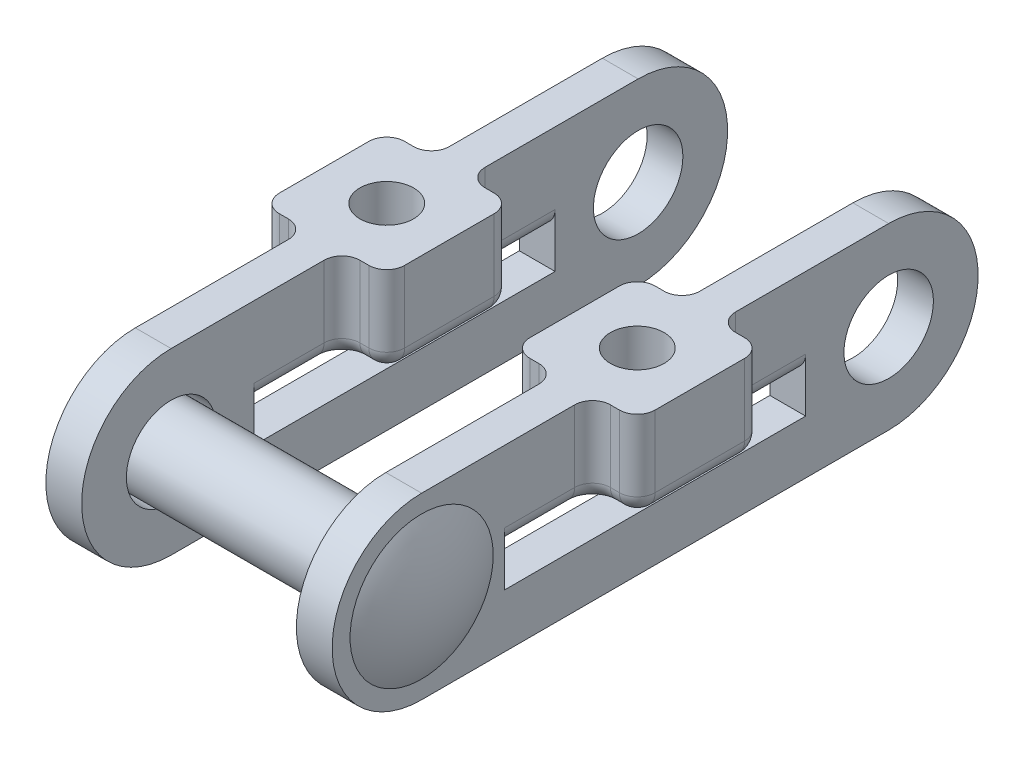
SolidWorks part; units mm, degrees
material "Alloy Steel"
ref_plane "Front Plane" through (0, 0, 0) normal (0, 0, 1) x (1, 0, 0)
ref_plane "Top Plane" through (0, 0, 0) normal (0, 1, 0) x (1, 0, 0)
ref_plane "Right Plane" through (0, 0, 0) normal (1, 0, 0) x (0, 0, -1)
sketch "Sketch1" plane through (0, 0, 0) normal (1, 0, 0) x (0, 0, -1)
  line L0 (0, 5) -> (26.1, 5)
  line L1 (26.1, -5) -> (0, -5)
  arc A0 (0, 5) -> (0, -5) centre (0, 0) ccw
  arc A1 (26.1, -5) -> (26.1, 5) centre (26.1, 0) ccw
  circle A2 centre (0, 0) radius 2.5
  circle A3 centre (26.1, 0) radius 2.5
  dimension "D1" = 26.1
  dimension "D2" = 10
  dimension "D3" = 5
extrude "Boss-Extrude1" add sketch "Sketch1" along normal blind 2
sketch "Sketch3" plane through (0, 5, 0) normal (0, 1, 0) x (1, 0, 0)
  line L0 (2, 0) -> (0, 0) construction
  line L1 (-2.5, 16.55) -> (4.5, 16.55)
  line L2 (-2.5, 16.55) -> (-2.5, 9.55)
  line L3 (-2.5, 9.55) -> (4.5, 9.55)
  line L4 (4.5, 16.55) -> (4.5, 9.55)
  line L5 (-2.5, 16.55) -> (4.5, 9.55) construction
  line L6 (-2.5, 9.55) -> (4.5, 16.55) construction
  line L7 (2, 26.1) -> (2, 0) construction
  point P0 (1, 13.05)
  point P7 (1, 0)
  point P10 (2, 13.05)
  dimension "D1" = 7
  dimension "D2" = 7
extrude "Boss-Extrude2" add sketch "Sketch3" against normal blind 5
sketch "Sketch4" plane through (0, 5, 0) normal (0, 1, 0) x (1, 0, 0)
  line L0 (4.5, 9.55) -> (4.5, 16.55) construction
  line L1 (2, 0) -> (0, 0) construction
  circle A0 centre (1, 13.05) radius 1.5
  point P4 (4.5, 13.05)
  point P7 (1, 0)
  dimension "D1" = 3
extrude "Cut-Extrude1" cut sketch "Sketch4" against normal blind 5
sketch "Sketch5" plane through (0, 0, 0) normal (0, 1, 0) x (1, 0, 0)
  line L0 (2, 26.1) -> (2, 16.55) construction
  line L1 (0, 4.6409) -> (2, 4.6409)
  line L2 (0, 4.6409) -> (0, 21.4591)
  line L3 (0, 21.4591) -> (2, 21.4591)
  line L4 (2, 4.6409) -> (2, 21.4591)
  line L5 (0, 4.6409) -> (2, 21.4591) construction
  line L6 (0, 21.4591) -> (2, 4.6409) construction
  point P0 (1, 13.05)
extrude "Cut-Extrude2" cut sketch "Sketch5" against normal blind 2
fillet "Fillet1" radius 1 8 edges at (2, 2.5, -16.55) (4.5, 2.5, -16.55) (2, 2.5, -9.55) (4.5, 2.5, -9.55) (0, 2.5, -9.55) (0, 2.5, -16.55) (-2.5, 2.5, -9.55) (-2.5, 2.5, -16.55)
fillet "Fillet2" radius 1 18 edges at (2, 0, -19.5045) (2.2929, 0, -16.8429) (3.25, 0, -16.55) (4.2071, 0, -16.2571) (4.5, 0, -13.05) (4.2071, 0, -9.8429) (3.25, 0, -9.55) (2, 0, -6.5955) (0, 0, -6.5955) (-0.2929, 0, -9.2571) (-1.25, 0, -9.55) (-2.2071, 0, -9.8429) (-2.5, 0, -13.05) (-2.2071, 0, -16.2571) (-1.25, 0, -16.55) (0, 0, -19.5045) (2.2929, 0, -9.2571) (-0.2929, 0, -16.8429)
pattern_linear "LPattern1" count 2 spacing 14 along (-1, 0, 0) of bodies 104
sketch "Sketch6" plane through (2, 0, 0) normal (1, 0, 0) x (0, 0, -1)
  circle A0 centre (0, 0) radius 2.25
  dimension "D1" = 4.5
extrude "Boss-Extrude3" add sketch "Sketch6" against normal up to surface (16 mm away) separate body up to face at (-14, 0, -28.6)
ref_plane "Plane1" through (0, 0, 0) normal (0, 1, 0) x (1, 0, 0)
sketch "Sketch7" plane through (0, 0, 0) normal (0, 1, 0) x (1, 0, 0)
  line L5 (2, -2.25) -> (2, 2.25) construction
  line L6 (-14, 2.25) -> (-14, -2.25) construction
  line L7 (2, -2.25) -> (2, 2.25) construction
  line L8 (-14, 2.25) -> (-14, -2.25) construction
  line L15 (-9.5, 13.05) -> (-2.5, 13.05) construction
  line L16 (-9.5, 10.55) -> (-9.5, 15.55) construction
  line L17 (-2.5, 15.55) -> (-2.5, 10.55) construction
  line L18 (-14, 0) -> (-14, -4)
  line L19 (-15, 0) -> (-14, 0)
  line L20 (3, 0) -> (2, 0)
  line L21 (2, 0) -> (2, -4)
  arc A3 (-15, 0) -> (-14, -4) centre (-6.5, 0) ccw
  arc A4 (3, 0) -> (2, -4) centre (-5.5, 0) cw
  dimension "D1" = 4
  dimension "D2" = 4
  dimension "D3" = 1
  dimension "D5" = 8.5
  dimension "D6" = 8.5
  dimension "D4" = 1
revolve "Revolve3" add sketch "Sketch7<4>" angle 360 about L20
sketch "Sketch7<4>" plane through (0, 0, 0) normal (0, 1, 0) x (1, 0, 0) same geometry as "Sketch7"
revolve "Revolve4" add sketch "Sketch7" angle 360 about L19
ref_plane "Plane2" through (-6, 0, 0) normal (1, 0, 0) x (0, 0, -1)
